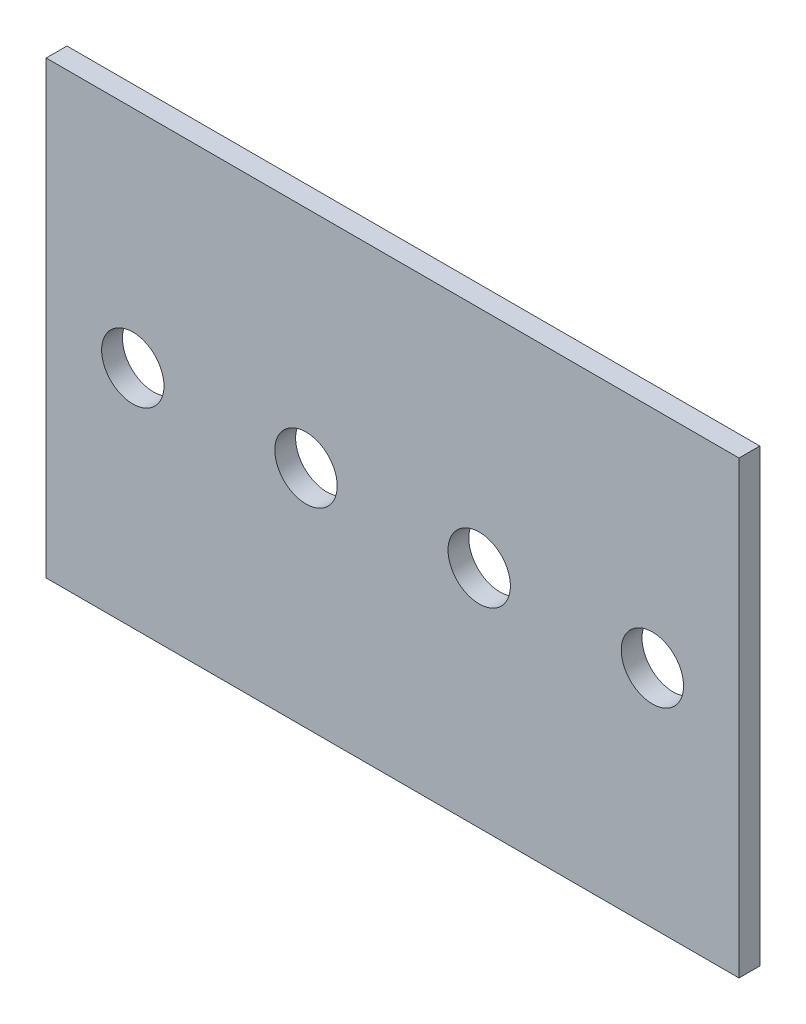
SolidWorks part; units mm, degrees
material "Простая углеродистая сталь"
ref_plane "Спереди" through (0, 0, 0) normal (0, 0, 1) x (1, 0, 0)
ref_plane "Сверху" through (0, 0, 0) normal (0, 1, 0) x (1, 0, 0)
ref_plane "Справа" through (0, 0, 0) normal (1, 0, 0) x (0, 0, -1)
sketch "Эскиз1" plane through (0, 0, 0) normal (0, 0, 1) x (1, 0, 0)
  line L5 (0, 0) -> (200, 0)
  line L6 (0, 0) -> (0, -130)
  line L7 (0, -130) -> (200, -130)
  line L8 (200, 0) -> (200, -130)
  line L9 (100, -130) -> (100, 0) construction
  line L10 (0, -65) -> (200, -65) construction
  circle A0 centre (75, -65) radius 9
  circle A1 centre (25, -65) radius 9
  circle A2 centre (125, -65) radius 9
  circle A3 centre (175, -65) radius 9
  point P197 (100, -65)
  dimension "D3" = 18
  dimension "D5" = 2
  dimension "D6" = 50
  dimension "D1" = 200
  dimension "D2" = 130
  dimension "D4" = 25
base flange "Базовая кромка1" sketch "Эскиз1" thickness 6 reverse thickness direction no parameters "D1"=1
sketch "Сгиб-Линии1" [suppressed] plane through (0, 0, 0) normal (0, 1, 0) x (1, 0, 0)
sketch "Граничная рамка1" [suppressed] plane through (0, 0, 0) normal (0, 1, 0) x (1, 0, 0)
sheet metal parameters "Листовой металл1" thickness 6 parameters "D1"=1
flat pattern "Развертка1" [suppressed]
sketch "Сгиб-Линии2" plane through (0, 0, 0) normal (0, 1, 0) x (1, 0, 0)
sketch3d "Граничная рамка2" [suppressed]
  line L0 (0, -130, 0) -> (200, -130, 0) construction
  line L1 (0, 0, 0) -> (200, 0, 0) construction
  line L2 (0, -130, 0) -> (0, 0, 0) construction
  line L3 (200, -130, 0) -> (200, 0, 0) construction
